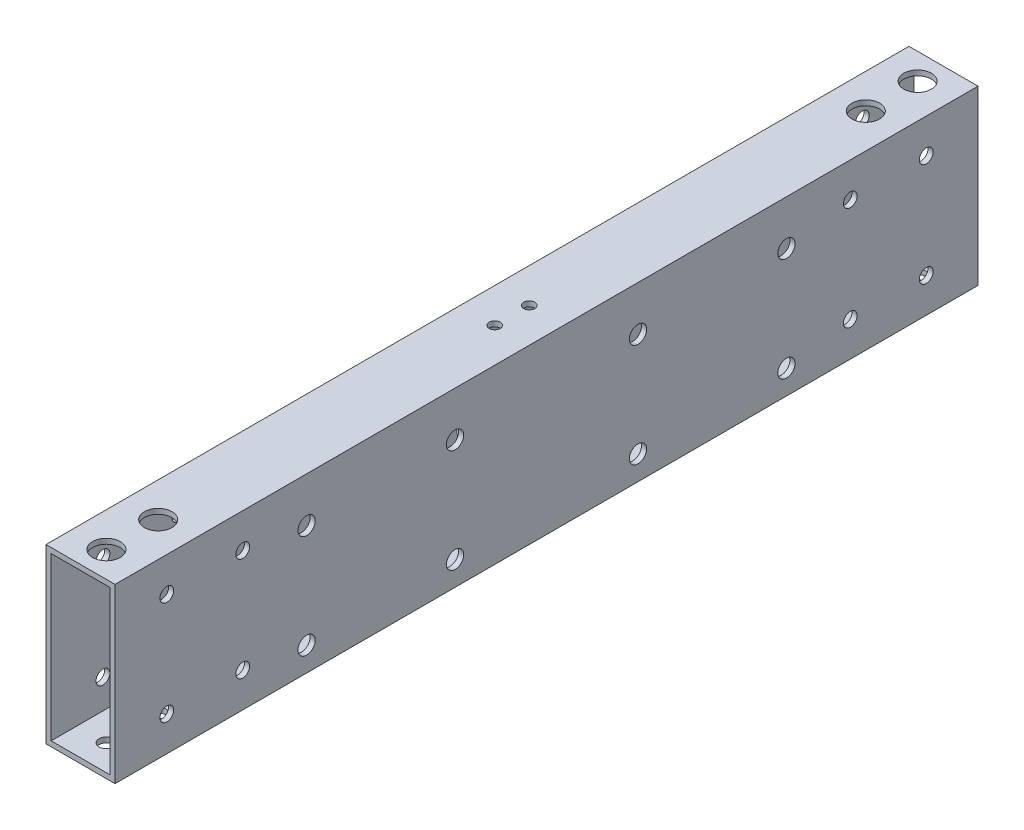
SolidWorks part; units mm, degrees
ref_plane "前视基准面" through (0, 0, 0) normal (0, 0, 1) x (1, 0, 0)
ref_plane "上视基准面" through (0, 0, 0) normal (0, 1, 0) x (1, 0, 0)
ref_plane "右视基准面" through (0, 0, 0) normal (1, 0, 0) x (0, 0, -1)
sketch "草图1" plane through (0, 0, 0) normal (0, 0, 1) x (1, 0, 0)
  line L0 (-8.5, 23.5) -> (8.5, 23.5)
  line L1 (-10, -25) -> (10, -25)
  line L2 (-10, -25) -> (-10, 25)
  line L3 (-10, 25) -> (10, 25)
  line L4 (10, -25) -> (10, 25)
  line L5 (-10, -25) -> (10, 25) construction
  line L6 (-10, 25) -> (10, -25) construction
  line L11 (8.5, -23.5) -> (8.5, 23.5)
  line L12 (-8.5, -23.5) -> (8.5, -23.5)
  line L13 (-8.5, -23.5) -> (-8.5, 23.5)
  point P9 (0, 0)
  dimension "D1" = 50
  dimension "D2" = 20
  dimension "D3" = 1.5
extrude "凸台-拉伸1" add sketch "草图1" against normal blind 250
sketch "草图2" plane through (-10, 0, 0) normal (-1, 0, 0) x (0, 0, 1)
  line L0 (-125, 20) -> (-125, -49980) construction
  line L1 (-250, 25) -> (0, 25) construction
  line L2 (-250, 25) -> (0, 25) construction
  line L11 (-55.5, -18) -> (-98.5, -18) construction
  line L13 (-55.5, -18) -> (-55.5, 12) construction
  line L14 (-55.5, 12) -> (-98.5, 12) construction
  line L15 (-98.5, -18) -> (-98.5, 12) construction
  line L16 (-55.5, -18) -> (-98.5, 12) construction
  line L17 (-55.5, 12) -> (-98.5, -18) construction
  line L18 (-71.3284, -3) -> (-50071.3284, -3) construction
  line L19 (-77, -3) -> (-77, 49997) construction
  line L20 (-194.5, 12) -> (-151.5, -18) construction
  line L21 (-194.5, -18) -> (-151.5, 12) construction
  line L22 (-151.5, -18) -> (-151.5, 12) construction
  line L23 (-194.5, 12) -> (-151.5, 12) construction
  line L24 (-194.5, -18) -> (-194.5, 12) construction
  line L25 (-194.5, -18) -> (-151.5, -18) construction
  line L26 (0, -25) -> (0, 25) construction
  circle A16 centre (-55.5, 12) radius 2.5
  circle A17 centre (-98.5, 12) radius 2.5
  circle A18 centre (-98.5, -18) radius 2.5
  circle A19 centre (-55.5, -18) radius 2.5
  circle A20 centre (-194.5, -18) radius 2.5
  circle A21 centre (-151.5, -18) radius 2.5
  circle A22 centre (-151.5, 12) radius 2.5
  circle A23 centre (-194.5, 12) radius 2.5
  point P4 (-125, 25)
  point P5 (-77, -3)
  point P28 (-173, -3)
  dimension "D4" = 5
  dimension "D5" = 77
  dimension "D2" = 43
  dimension "D1" = 30
  dimension "D3" = 28
extrude "切除-拉伸1" cut sketch "草图2" against normal through all
sketch "草图3" plane through (0, 25, 0) normal (0, 1, 0) x (1, 0, 0)
  line L0 (-10, 30) -> (49990, 30) construction
  line L2 (10, 0) -> (-10, 0) construction
  line L3 (0, 0) -> (0, 50000) construction
  line L4 (10, 125) -> (50010, 125) construction
  line L5 (10, 250) -> (10, 0) construction
  circle A0 centre (0, 22.5) radius 2.1
  circle A1 centre (0, 7.5) radius 2.1
  circle A2 centre (0, 242.5) radius 2.1
  circle A3 centre (0, 227.5) radius 2.1
  point P6 (0, 0)
  point P15 (10, 125)
  dimension "D2" = 4.2
  dimension "D3" = 4.2
  dimension "D1" = 30
  dimension "D4" = 15
  dimension "D5" = 7.5
extrude "切除-拉伸2" cut sketch "草图3" against normal through all
sketch "草图4" plane through (0, 25, 0) normal (0, 1, 0) x (1, 0, 0)
  line L0 (0, 250) -> (0, -49750) construction
  line L1 (10, 250) -> (-10, 250) construction
  line L2 (-10, 125) -> (49990, 125) construction
  line L3 (-10, 250) -> (-10, 0) construction
  circle A0 centre (0, 130) radius 1.6
  circle A1 centre (0, 120) radius 1.6
  point P4 (0, 250)
  point P9 (-10, 125)
  dimension "D1" = 3.2
  dimension "D2" = 10
extrude "切除-拉伸3" cut sketch "草图4" against normal blind 10
sketch "草图5" plane through (0, 25, 0) normal (0, 1, 0) x (1, 0, 0)
  line L0 (10, 125) -> (50010, 125) construction
  line L1 (10, 250) -> (10, 0) construction
  circle A0 centre (0, 22.5) radius 4
  circle A1 centre (0, 7.5) radius 4
  circle A2 centre (0, 242.5) radius 4
  circle A3 centre (0, 227.5) radius 4
  point P10 (10, 125)
  dimension "D1" = 8
  dimension "D2" = 8
extrude "切除-拉伸4" cut sketch "草图5" against normal blind 10
sketch "草图6" plane through (-10, 0, 0) normal (-1, 0, 0) x (0, 0, 1)
  line L0 (-125, 25) -> (-125, -75.8071) construction
  line L1 (-250, 25) -> (0, 25) construction
  circle A0 centre (-125, -4) radius 7.5
  dimension "D1" = 15
  dimension "D2" = 4
extrude "切除-拉伸5" cut sketch "草图6" against normal blind 10
sketch "草图7" plane through (-10, 0, 0) normal (-1, 0, 0) x (0, 0, 1)
  line L0 (-250, 0) -> (0, 0) construction
  line L1 (-250, 25) -> (-250, -25) construction
  line L2 (-125, 25) -> (-125, -25) construction
  line L3 (-250, 25) -> (0, 25) construction
  line L4 (-250, -25) -> (0, -25) construction
  line L5 (-250, 15) -> (0, 15) construction
  line L6 (0, 25) -> (0, -25) construction
  line L7 (-250, -15) -> (0, -15) construction
  circle A0 centre (-235, 15) radius 2
  circle A1 centre (-213, 15) radius 2
  circle A2 centre (-235, -15) radius 2
  circle A3 centre (-213, -15) radius 2
  circle A5 centre (-37, -15) radius 2
  circle A6 centre (-15, -15) radius 2
  circle A7 centre (-37, 15) radius 2
  circle A8 centre (-15, 15) radius 2
  dimension "D3" = 4
  dimension "D1" = 15
  dimension "D2" = 15
  dimension "D4" = 22
  dimension "D5" = 15
extrude "切除-拉伸6" cut sketch "草图7" against normal through all
sketch "草图8" plane through (10, 0, 0) normal (1, 0, 0) x (0, 0, -1)
  line L0 (125, 25) -> (125, -58.3352) construction
  line L1 (250, 25) -> (0, 25) construction
  line L2 (138.5, 25) -> (138.5, -3.973)
  line L3 (138.5, 25) -> (111.5, 25)
  line L4 (125, 25) -> (125, -3.973)
  line L5 (138.5, -3.973) -> (111.5, -3.973)
  line L6 (111.5, 25) -> (111.5, -3.973)
  line M24 (250, 25) -> (0, 25)
  dimension "D1" = 27
extrude "切除-拉伸7" [suppressed] cut sketch "草图8" against normal blind 37 contours L5 L2 L4 M24 | L3 L6 L5 L4
equation "\"3。2\"=3.21956"
